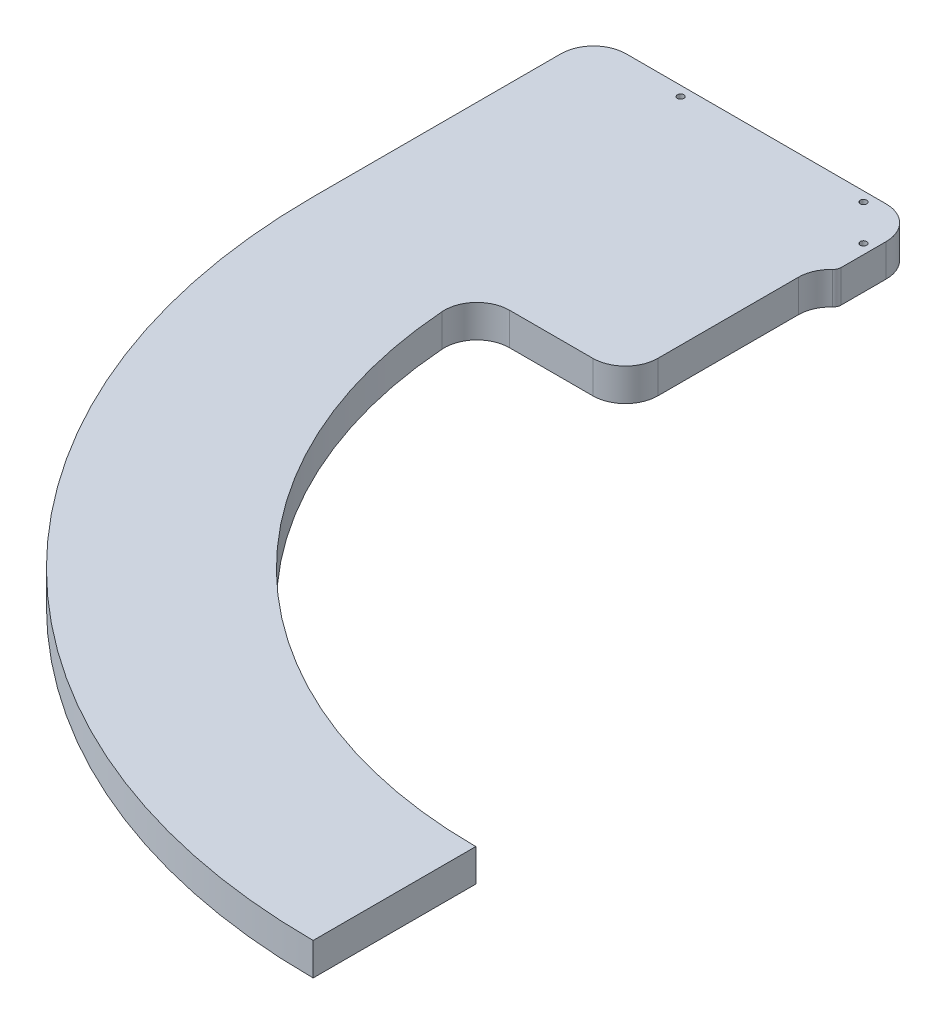
SolidWorks part; units mm, degrees
ref_plane "Front Plane" through (0, 0, 0) normal (0, 0, 1) x (1, 0, 0)
ref_plane "Top Plane" through (0, 0, 0) normal (0, 1, 0) x (1, 0, 0)
ref_plane "Right Plane" through (0, 0, 0) normal (1, 0, 0) x (0, 0, -1)
sketch "Sketch1" plane through (0, 0, 0) normal (0, 1, 0) x (1, 0, 0)
  line L0 (239.407, 1980.365) -> (168.407, 1980.365) construction
  line L5 (242.107, 1980.365) -> (165.907, 1980.365) construction
  line L6 (242.107, 1980.365) -> (242.107, 1898.165) construction
  line L9 (242.107, 1980.365) -> (146.1085, 1980.365) construction
  line L10 (146.1085, 1980.365) -> (146.1085, 1898.165)
  line L11 (242.107, 1951.1726) -> (242.107, 1977.665) construction
  line L12 (196.1085, 1893.8062) -> (196.1085, 1901.9287) construction
  line L13 (165.907, 1898.165) -> (165.907, 1980.365) construction
  line L14 (242.107, 1898.165) -> (165.907, 1898.165) construction
  line L15 (242.107, 1980.365) -> (242.107, 1898.165) construction
  line L16 (344.107, 1750.1665) -> (344.107, 1700.1665)
  line L17 (344.107, 1898.165) -> (344.107, 1700.1665) construction
  line L18 (185.0204, 1898.165) -> (201.5333, 1898.165) construction
  line L19 (165.907, 1977.665) -> (165.907, 1919.1243) construction
  line L21 (242.107, 1898.165) -> (196.1085, 1898.165)
  line L22 (242.107, 1898.165) -> (242.107, 1959.365)
  line L23 (295.1102, 1700.1665) -> (369.3843, 1700.1665) construction
  line L24 (242.107, 1959.365) -> (246.107, 1959.365)
  line L25 (246.107, 1959.365) -> (246.107, 1984.365)
  line L26 (246.107, 1984.365) -> (146.1085, 1984.365)
  line L27 (146.1085, 1984.365) -> (146.1085, 1980.365)
  arc A0 (344.107, 1700.1665) -> (146.1085, 1898.165) centre (344.107, 1898.165) cw
  arc A1 (196.1085, 1898.165) -> (344.107, 1750.1665) centre (344.107, 1898.165) ccw
  dimension "D1" = 50
  dimension "D2" = 4
  dimension "D3" = 4
  dimension "D4" = 25
extrude "Boss-Extrude1" add sketch "Sketch1" against normal blind 10
hole_wizard "Ø2.0mm Dowel Hole1" positions "Sketch2" profile "Sketch3" hole size "Ø2.0" standard "ISO" end condition through all
sketch "Sketch2" plane through (0, 0, 0) normal (0, 1, 0) x (1, 0, 0)
  line L0 (175.907, 1981.365) -> (232.107, 1981.365) construction
  line L1 (232.107, 1981.365) -> (243.107, 1981.365) construction
  line L2 (243.107, 1981.365) -> (243.107, 1970.365) construction
  line L4 (168.407, 1980.365) -> (239.407, 1980.365) construction
  line L5 (242.107, 1977.665) -> (242.107, 1951.1726) construction
  line L6 (165.907, 1919.1243) -> (165.907, 1977.665) construction
  point P0 (175.907, 1981.365)
  point P2 (232.107, 1981.365)
  point P4 (243.107, 1970.365)
  dimension "D1" = 1
  dimension "D2" = 1
  dimension "D3" = 10
  dimension "D4" = 10
  dimension "D5" = 10
sketch "Sketch3" plane through (175.907, 0, -1981.365) normal (1, 0, 0) x (0, 0, 1)
  line L0 (0, 0) -> (0, 10)
  line L1 (0, 10) -> (1, 10)
  line L2 (1, 10) -> (1, 0)
  line L5 (1, 0) -> (0, 0)
  line L11 (0, -6.35) -> (0, 107.95) construction
  dimension "Thru Hole Dia." = 2
  dimension "Thru Hole Depth" = 10
fillet "Fillet1" radius 10 5 edges at (196.1085, -5, -1898.165) (146.1085, -5, -1984.365) (246.107, -5, -1984.365) (242.107, -5, -1959.365) (242.107, -5, -1898.165)
fillet "Fillet2" radius 2.5 1 edges at (246.107, -5, -1959.365)
